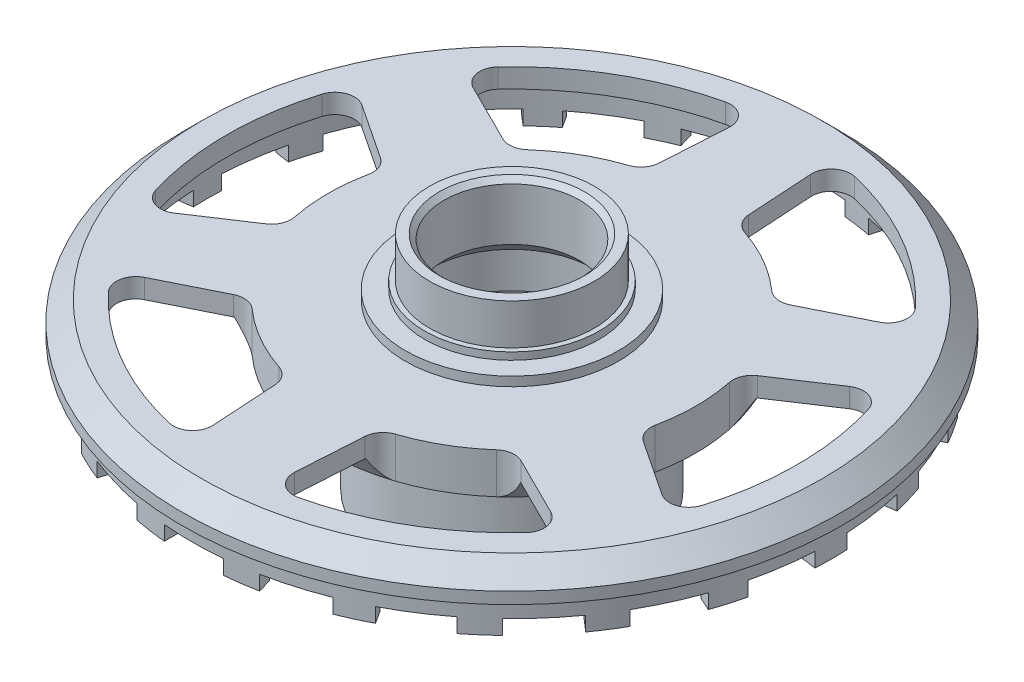
SolidWorks part; units mm, degrees
ref_plane "Front Plane" through (0, 0, 0) normal (0, 0, 1) x (1, 0, 0)
ref_plane "Top Plane" through (0, 0, 0) normal (0, 1, 0) x (1, 0, 0)
ref_plane "Right Plane" through (0, 0, 0) normal (1, 0, 0) x (0, 0, -1)
ref_axis "Axis1" through (0, 0, 0) along (0, 1, 0)
sketch "Sketch1" plane through (0, 0, 0) normal (0, 0, 1) x (1, 0, 0)
  line L0 (-32.95, 8) -> (-32.95, 4.5)
  line L2 (-32.95, 4.5) -> (-31.45, 4.5)
  line L3 (-31.45, 4.5) -> (-31.45, 8.2)
  line L4 (-32.95, 8) -> (-34, 8)
  line L5 (-34, 8) -> (-34, 8.5)
  line L7 (-11, 12.15) -> (-9, 12.15)
  line L8 (-9, 12.15) -> (-9, 12.9)
  line L9 (-9, 12.9) -> (-8.5, 12.9)
  line L10 (-8.5, 12.9) -> (-8.5, 17.1)
  line L11 (-8.5, 17.1) -> (-7, 17.1)
  line L12 (-7, 17.1) -> (-7, 11.2)
  line L15 (0, 0) -> (0, -50000) construction
  line L16 (-30.45, 9.2) -> (-31.45, 8.2)
  line L18 (-8.5, 9.7) -> (-8.5, 6)
  line L25 (-12.99, 4) -> (-12.49, 4)
  line L29 (-20.2602, 9.2) -> (-30.45, 9.2)
  line L32 (-34, 9.2) -> (-34, 8.5)
  line L34 (-32, 11.2) -> (-11, 11.2)
  line L35 (-34, 9.2) -> (-32, 11.2)
  line L36 (-11, 12.15) -> (-11, 11.2)
  line L38 (20.75, 6) -> (-20.75, 6) construction
  line L39 (-20.2602, 9.2) -> (-18.99, 7)
  line L40 (-18.99, 7) -> (-12.99, 7)
  line L41 (-12.99, 7) -> (-12.99, 4)
  line L44 (-12.49, 4) -> (-12.49, -6)
  line L45 (-12.49, -6) -> (-9, -6)
  line L46 (-9, -6) -> (-9, 6)
  line L47 (-9, 6) -> (-8.5, 6)
  line L48 (8.2033, 6) -> (-8.2033, 6) construction
  line L49 (-8.2033, -6) -> (8.2033, -6) construction
  line L50 (12.75, 4) -> (-12.75, 4) construction
  line L51 (-7, 11.2) -> (-8.5, 9.7)
  point P6 (-31.45, 9.2)
  point P19 (-34, 11.2)
  dimension "D1" = 3.5
  dimension "D2" = 1.5
  dimension "D3" = 17
  dimension "D4" = 4.2
  dimension "D5" = 0.75
  dimension "D6" = 0.5
  dimension "D7" = 1.5
  dimension "D8" = 135
  dimension "D10" = 65.9
  dimension "D11" = 22
  dimension "D12" = 0.5
  dimension "D13" = 18
  dimension "D15" = 0.5
  dimension "D16" = 0.95
  dimension "D17" = 6
  dimension "D18" = 0.5
  dimension "D19" = 2
  dimension "D20" = 3.2
  dimension "D21" = 1
  dimension "D22" = 120
  dimension "D23" = 24.98
revolve "Revolve1" add sketch "Sketch1" angle 360 about L15
sketch "Sketch2" plane through (0, 0, 0) normal (0, 0, 1) x (1, 0, 0)
  line L1 (-3.05, -0.7629) -> (3.05, -0.7629)
  line L2 (-3.05, -0.7629) -> (-3.05, 6)
  line L3 (-3.05, 6) -> (3.05, 6)
  line L4 (3.05, -0.7629) -> (3.05, 6)
  line L5 (-32.95, 8) -> (32.95, 8) construction
  point P4 (0, -0.7629)
  dimension "D1" = 6.1
  dimension "D2" = 2
extrude "Cut-Extrude2" cut sketch "Sketch2" along normal through all from offset 20
pattern_circular "CirPattern1" count 22 over 360 about axis through (0, 0, 0) along (0, 1, 0) of "Cut-Extrude2"
sketch "Sketch4" plane through (0, 0, 0) normal (0, 1, 0) x (1, 0, 0)
  circle A0 centre (-16, 0) radius 2.06
  dimension "D1" = 4.12
  dimension "D2" = 16
extrude "Cut-Extrude3" cut sketch "Sketch4" along normal blind 3 from surface starting at face at (-12.99, 7, 0)
pattern_circular "CirPattern2" count 22 over 360 about axis through (0, 0, 0) along (0, 1, 0) of "Cut-Extrude3"
sketch "Sketch5" plane through (0, 0, 0) normal (0, 1, 0) x (1, 0, 0)
  circle A0 centre (0, 0) radius 16
extrude "Cut-Extrude-Thin1" cut sketch "Sketch5" along normal up to surface (10 mm away) thin up to face at (-13.94, 10, 0) thin type mid plane wall 2
chamfer "Chamfer1" distance 0.5 angle 45 1 edges at (-7, 17.1, 0)
sketch "Sketch6" plane through (0, 0, 0) normal (0, 1, 0) x (1, 0, 0)
  line L0 (0, 0) -> (-50000, 0) construction
  line L1 (-27.2859, -11.0807) -> (-18.2867, -5.1202)
  line L2 (-18.2867, 5.1202) -> (-27.2859, 11.0807)
  arc A0 (-27.2859, -11.0807) -> (-27.2859, 11.0807) centre (0, 0) cw
  arc A1 (-18.2867, -5.1202) -> (-18.2867, 5.1202) centre (0, 0) cw
  circle A2 centre (0, 0) radius 30.45 construction
  circle A3 centre (0, 0) radius 18.99 construction
  point P9 (-29.45, 0)
  point P10 (-18.99, 0)
  dimension "D1" = 1
extrude "Cut-Extrude4" cut sketch "Sketch6" along normal through all
fillet "Fillet1" radius 2 4 edges at (-27.2859, 10.2, 11.0807) (-18.2867, 9.1, 5.1202) (-18.2867, 9.1, -5.1202) (-27.2859, 10.2, -11.0807)
pattern_circular "CirPattern3" count 6 over 360 about axis through (0, 0, 0) along (0, 1, 0) of "Cut-Extrude4", "Fillet1"
chamfer "Chamfer2" distance 0.25 angle 45 2 edges at (-9, -6, 0) (-12.49, -6, 0)
